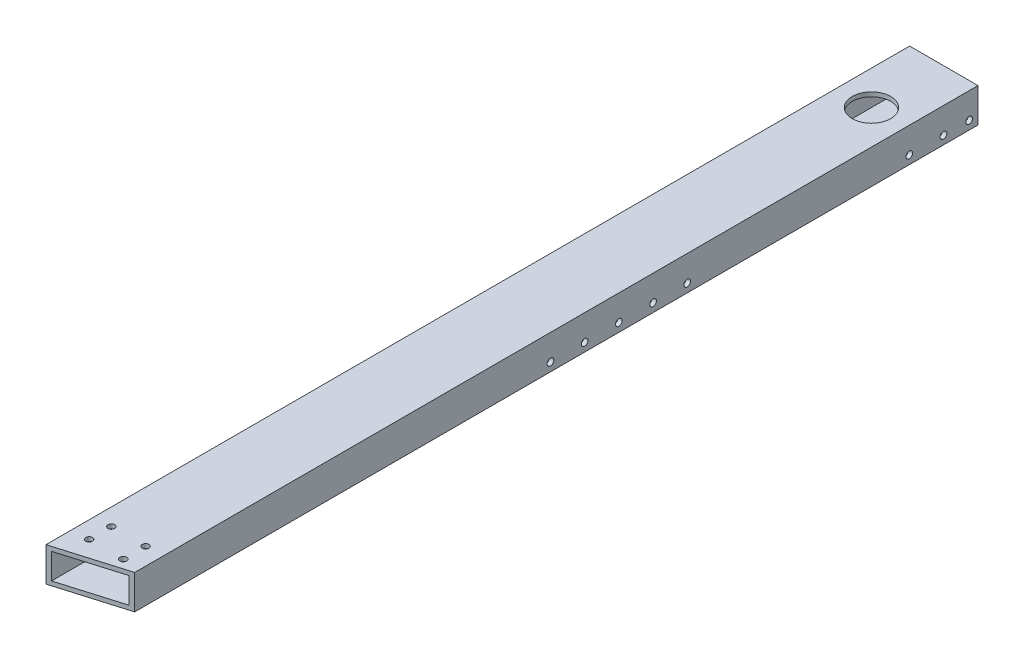
SolidWorks part; units mm, degrees
ref_plane "Front Plane" through (0, 0, 0) normal (0, 0, 1) x (1, 0, 0)
ref_plane "Top Plane" through (0, 0, 0) normal (0, 1, 0) x (1, 0, 0)
ref_plane "Right Plane" through (0, 0, 0) normal (1, 0, 0) x (0, 0, -1)
sketch "Sketch1" plane through (0, 0, 0) normal (0, 0, 1) x (1, 0, 0)
  line L0 (-22.225, 9.525) -> (22.225, 9.525)
  line L2 (-25.4, 12.7) -> (25.4, 12.7)
  line L3 (-25.4, 12.7) -> (-25.4, -12.7)
  line L4 (-25.4, -12.7) -> (25.4, -12.7)
  line L5 (25.4, 12.7) -> (25.4, -12.7)
  line L10 (22.225, 9.525) -> (22.225, -9.525)
  line L11 (-22.225, -9.525) -> (22.225, -9.525)
  line L12 (-22.225, 9.525) -> (-22.225, -9.525)
  point P12 (0, 12.7)
  point P14 (25.4, 0)
  dimension "Wall Thickness" = 3.175
  dimension "Outside Width" = 50.8
  dimension "Outside Height" = 25.4
  dimension "Inside Height" = 19.05
  dimension "Inside Width" = 44.45
sketch "Sketch2" plane through (0, 0, 0) normal (1, 0, 0) x (0, 0, -1)
  line L0 (320.675, 0) -> (-320.675, 0)
  point P4 (0, 0)
  point P7 (-320.675, 0)
  point P10 (320.675, 0)
  dimension "Length" = 641.35
sketch "Sketch3" plane through (0, 0, 0) normal (0, 0, 1) x (1, 0, 0)
  line L21 (25.4, 12.7) -> (-25.4, 12.7)
  line L22 (25.4, -12.7) -> (25.4, 12.7)
  line L23 (-25.4, -12.7) -> (25.4, -12.7)
  line L24 (-25.4, 12.7) -> (-25.4, -12.7)
  line L25 (25.4, 12.7) -> (-25.4, 12.7)
  line L26 (25.4, -12.7) -> (25.4, 12.7)
  line L27 (-25.4, -12.7) -> (25.4, -12.7)
  line L28 (-25.4, 12.7) -> (-25.4, -12.7)
  line L29 (22.225, 9.525) -> (-22.225, 9.525)
  line L30 (22.225, -9.525) -> (22.225, 9.525)
  line L31 (-22.225, -9.525) -> (22.225, -9.525)
  line L32 (-22.225, 9.525) -> (-22.225, -9.525)
  line L33 (22.225, 9.525) -> (-22.225, 9.525)
  line L34 (22.225, -9.525) -> (22.225, 9.525)
  line L35 (-22.225, -9.525) -> (22.225, -9.525)
  line L36 (-22.225, 9.525) -> (-22.225, -9.525)
  dimension "D1" = 0
  dimension "D2" = 0
extrude "Boss-Extrude1" add sketch "Sketch3" along normal up to vertex (320.675 mm away) and the other way up to vertex (320.675 mm away) up to point (0, 0, 320.675) other way up to point (0, 0, -320.675)
sketch "Drawing Reference" plane through (0, 0, 0) normal (1, 0, 0) x (0, 0, -1)
  line L0 (-320.675, 0) -> (320.675, 0) construction
  line L1 (0, -12.7) -> (0, 12.7) construction
  line L2 (-320.675, -12.7) -> (320.675, -12.7) construction
  line L5 (-320.675, 12.7) -> (320.675, 12.7) construction
  point P7 (-284.099, 0)
  point P8 (284.099, 0)
  dimension "D1" = 36.576
sketch "Sketch4" plane through (0, 12.7, 0) normal (0, 1, 0) x (1, 0, 0)
  line L0 (-25.4, -320.675) -> (25.4, -305.6274)
  line L1 (25.4, -320.675) -> (25.4, 320.675) construction
  line L2 (25.4, -320.675) -> (-25.4, -320.675)
  dimension "D1" = 16.5
extrude "Cut-Extrude1" cut sketch "Sketch4" against normal through all and the other way through all flip side to cut
sketch "Sketch8" plane through (0, 12.7, 0) normal (0, 1, 0) x (1, 0, 0)
  line L0 (0, 320.675) -> (0, 266.954) construction
  line L1 (25.4, 320.675) -> (-25.4, 320.675) construction
  circle A0 centre (0, 266.954) radius 14.2875
  dimension "D1" = 53.721
extrude "Cut-Extrude2" cut sketch "Sketch8" against normal through all
sketch "Sketch9" plane through (0, 12.7, 0) normal (0, 1, 0) x (1, 0, 0)
  line L0 (-12.7762, -284.753) -> (12.6238, -284.753) construction
  line L1 (12.6238, -284.753) -> (12.6238, -301.263) construction
  line L2 (12.6238, -301.263) -> (-12.7762, -301.263) construction
  line L3 (-12.7762, -301.263) -> (-12.7762, -284.753) construction
hole_wizard "#10 Clearance Hole1" positions "Sketch10" profile "Sketch11" hole size "#10" standard "ANSI Inch"
sketch "Sketch10" plane through (0, 12.7, 0) normal (0, 1, 0) x (1, 0, 0)
  point P0 (-12.7762, -284.753)
  point P3 (12.6238, -284.753)
  point P6 (12.6238, -301.263)
  point P9 (-12.7762, -301.263)
sketch "Sketch11" plane through (-12.7762, 12.7, 284.753) normal (1, 0, 0) x (0, 0, 1)
  line L0 (0, 0) -> (0, 6.5757)
  line L1 (0, 6.5757) -> (2.4892, 5.08)
  line L2 (2.4892, 5.08) -> (2.4892, 0)
  line L5 (2.4892, 0) -> (0, 0)
  line L10 (0, 6.5757) -> (-2.4892, 5.08) construction
  line L11 (0, -6.35) -> (0, 107.95) construction
  dimension "Hole Dia." = 4.9784
  dimension "Hole Depth" = 5.08
  dimension "Drill Angle" = 118
hole_wizard "#10 Clearance Hole2" positions "Sketch12" profile "Sketch13" hole size "#10" standard "ANSI Inch" end condition through all
sketch "Sketch12" plane through (25.4, 0, 0) normal (1, 0, 0) x (0, 0, -1)
  point P0 (-282.5368, -18.8483)
  point P3 (-263.4868, -18.8483)
  point P6 (-238.125, -18.8483)
  point P9 (3.175, -6.35)
  point P12 (28.575, -6.35)
  point P15 (53.975, -6.35)
  point P18 (79.375, -6.35)
  point P21 (104.775, -6.35)
sketch "Sketch13" plane through (25.4, -18.8483, 282.5368) normal (0, 1, 0) x (0, 0, -1)
  line L0 (0, 0) -> (0, 50.8)
  line L1 (0, 50.8) -> (2.4892, 50.8)
  line L2 (2.4892, 50.8) -> (2.4892, 0)
  line L5 (2.4892, 0) -> (0, 0)
  line L11 (0, -6.35) -> (0, 107.95) construction
  dimension "Thru Hole Dia." = 4.9784
  dimension "Thru Hole Depth" = 50.8
hole_wizard "#10 Clearance Hole3" positions "Sketch14" profile "Sketch15" hole size "#10" standard "ANSI Inch"
sketch "Sketch14" plane through (25.4, 0, 0) normal (1, 0, 0) x (0, 0, -1)
  point P0 (269.6733, -6.3882)
  point P3 (295.0733, -6.3882)
  point P6 (314.1233, -6.3882)
sketch "Sketch15" plane through (25.4, -6.3882, -269.6733) normal (0, 1, 0) x (0, 0, -1)
  line L0 (0, 0) -> (0, 4.7977)
  line L1 (0, 4.7977) -> (2.4892, 3.302)
  line L2 (2.4892, 3.302) -> (2.4892, 0)
  line L5 (2.4892, 0) -> (0, 0)
  line L10 (0, 4.7977) -> (-2.4892, 3.302) construction
  line L11 (0, -6.35) -> (0, 107.95) construction
  dimension "Hole Dia." = 4.9784
  dimension "Hole Depth" = 3.302
  dimension "Drill Angle" = 118
equation "\"D1@Drawing Reference\"=\"Outside Width@Sketch1\" * 0.72"
